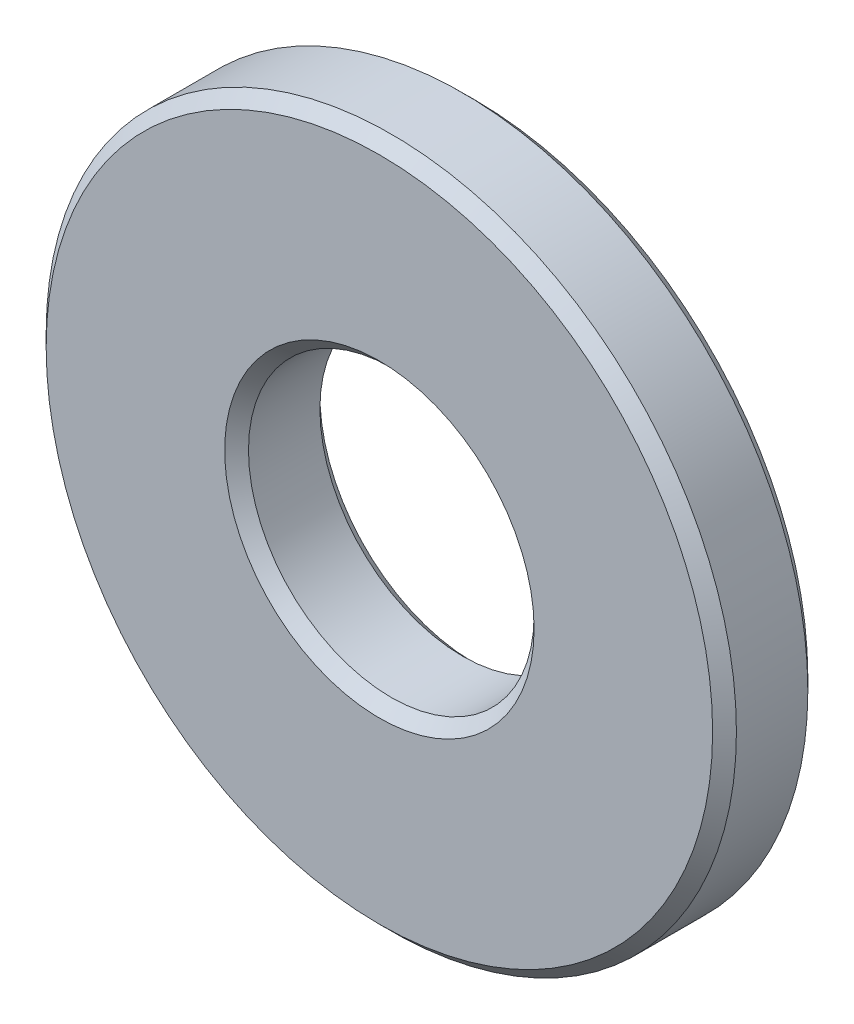
SolidWorks part; units mm, degrees
material "Plain Carbon Steel"
ref_plane "Front" through (0, 0, 0) normal (0, 0, 1) x (1, 0, 0)
ref_plane "Top" through (0, 0, 0) normal (0, 1, 0) x (1, 0, 0)
ref_plane "Right" through (0, 0, 0) normal (1, 0, 0) x (0, 0, -1)
ref_axis "Axis1" through (-84.4107, 0, 0) along (1, 0, 0)
ref_axis "Axis2" through (0, 64.3378, 0) along (0, -1, 0)
ref_axis "Axis3" through (0, 0, -102.329) along (0, 0, 1)
sketch "Sketch1" plane through (0, 0, 0) normal (0, 0, 1) x (1, 0, 0)
  circle A0 centre (0, 0) radius 29
  circle A1 centre (0, 0) radius 12
  dimension "D1" = 58
  dimension "D2" = 24
extrude "Boss-Extrude1" add sketch "Sketch1" along normal blind 8
chamfer "Chamfer1" distance 1 angle 45 2 edges at (12, 0, 0) (12, 0, 8)
chamfer "Chamfer2" distance 1 angle 45 2 edges at (29, 0, 0) (29, 0, 8)
ref_plane "Plane1" through (0, 0, 8) normal (0, 0, 1) x (1, 0, 0)
